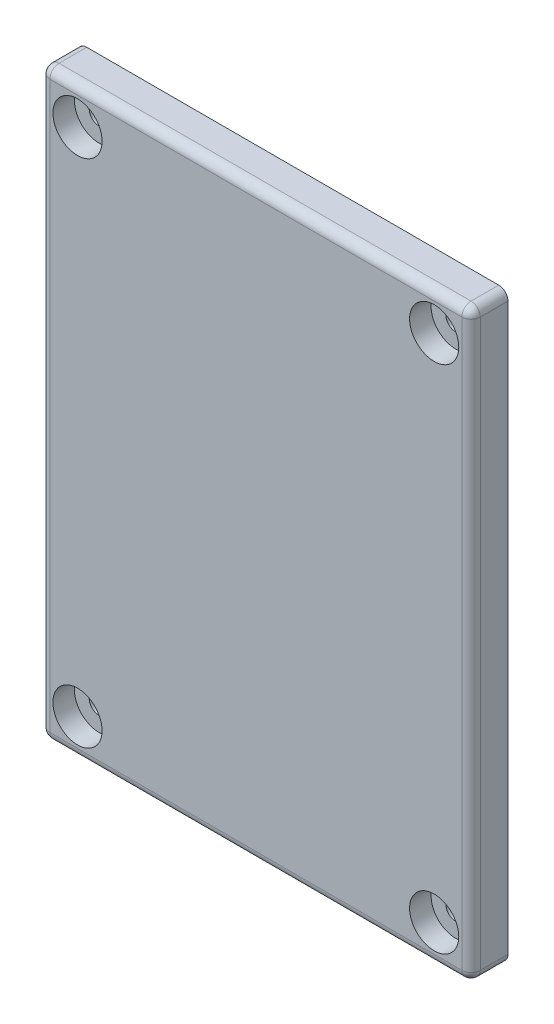
SolidWorks part; units mm, degrees
ref_plane "前视基准面" through (0, 0, 0) normal (0, 0, 1) x (1, 0, 0)
ref_plane "上视基准面" through (0, 0, 0) normal (0, 1, 0) x (1, 0, 0)
ref_plane "右视基准面" through (0, 0, 0) normal (1, 0, 0) x (0, 0, -1)
other "Configuration Table"
sketch "草图1" plane through (0, 0, 0) normal (0, 0, 1) x (1, 0, 0)
  line L1 (-33.102, 42.9718) -> (36.898, 42.9718)
  line L2 (-33.102, 42.9718) -> (-33.102, -52.0282)
  line L3 (-33.102, -52.0282) -> (36.898, -52.0282)
  line L4 (36.898, 42.9718) -> (36.898, -52.0282)
  dimension "D1" = 70
  dimension "D2" = 95
extrude "凸台-拉伸1" add sketch "草图1" along normal blind 6
sketch "草图2" plane through (0, 0, 6) normal (0, 0, 1) x (1, 0, 0)
  line L8 (-27.102, 36.9718) -> (-27.102, -46.0282)
  line L9 (-27.102, -46.0282) -> (30.898, -46.0282)
  line L10 (30.898, -46.0282) -> (30.898, 36.9718)
  line L11 (30.898, 36.9718) -> (-27.102, 36.9718)
  line L12 (-27.102, 36.9718) -> (-27.102, -46.0282) construction
  line L13 (-27.102, -46.0282) -> (30.898, -46.0282) construction
  line L14 (30.898, -46.0282) -> (30.898, 36.9718) construction
  line L15 (30.898, 36.9718) -> (-27.102, 36.9718) construction
  circle A0 centre (30.898, 36.9718) radius 4
  circle A1 centre (-27.102, 36.9718) radius 4
  circle A2 centre (30.898, -46.0282) radius 4
  circle A3 centre (-27.102, -46.0282) radius 4
  dimension "D2" = 8
  dimension "D3" = 8
  dimension "D4" = 8
  dimension "D5" = 8
  dimension "D1" = 6
extrude "切除-拉伸1" cut sketch "草图2" against normal blind 3.5
sketch "草图3" plane through (0, 0, 6) normal (0, 0, 1) x (1, 0, 0)
  circle A0 centre (30.898, 36.9718) radius 1.6
  circle A1 centre (-27.102, 36.9718) radius 1.6
  circle A2 centre (-27.102, -46.0282) radius 1.6
  circle A3 centre (30.898, -46.0282) radius 1.6
  dimension "D1" = 3.2
  dimension "D2" = 3.2
  dimension "D3" = 3.2
  dimension "D4" = 3.2
extrude "切除-拉伸2" cut sketch "草图3" against normal through all
shell "抽壳1" thickness 3 removed face at (32.498, -46.0282, 0)
fillet "圆角1" radius 1.5 8 edges at (-33.102, 42.9718, 3) (-33.102, -52.0282, 3) (-33.102, -4.5282, 6) (1.898, -52.0282, 6) (36.898, -52.0282, 3) (36.898, -4.5282, 6) (36.898, 42.9718, 3) (1.898, 42.9718, 6)
